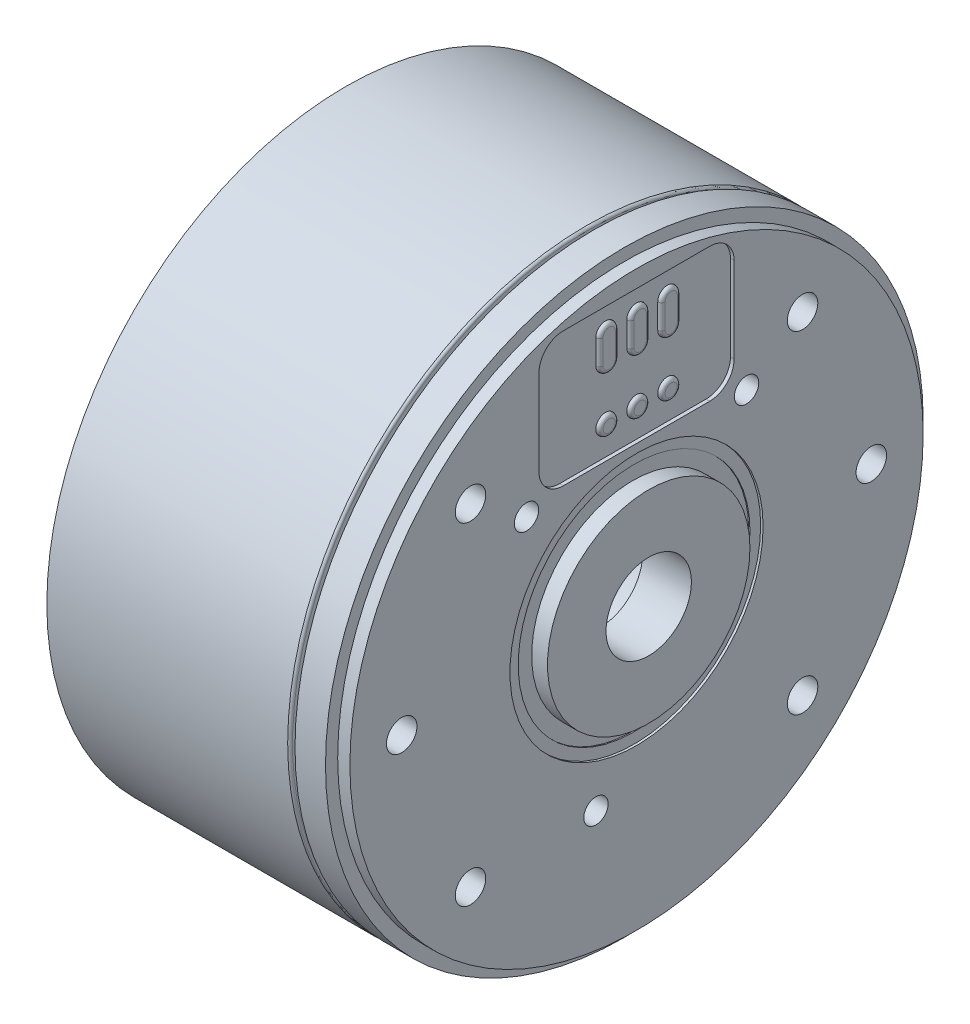
SolidWorks part; units mm, degrees
material "可锻铸铁"
ref_plane "前视基准面" through (0, 0, 0) normal (0, 0, 1) x (1, 0, 0)
ref_plane "上视基准面" through (0, 0, 0) normal (0, 1, 0) x (1, 0, 0)
ref_plane "右视基准面" through (0, 0, 0) normal (1, 0, 0) x (0, 0, -1)
sketch "草图2" plane through (0, 0, 0) normal (1, 0, 0) x (0, 0, -1)
  line L0 (0, 27.8437) -> (0, -27.533) construction
  line L1 (29.402, 0) -> (-30.6739, 0) construction
  line L2 (0, 0) -> (17.9277, 17.9277) construction
  circle A0 centre (0, 0) radius 24.5
  circle A1 centre (0, 0) radius 23.5
  circle A2 centre (0, 0) radius 12.5 construction
  circle A3 centre (0, 0) radius 9.5 construction
  circle A4 centre (0, 0) radius 6.3
  circle A5 centre (0, 9.5) radius 1.5
  circle A6 centre (9.5, 0) radius 1.5
  circle A7 centre (0, -9.5) radius 1.5
  circle A8 centre (-9.5, 0) radius 1.5
  circle A13 centre (8.8388, 8.8388) radius 1.5
  circle A14 centre (0, 0) radius 23.5
  circle A15 centre (8.8388, -8.8388) radius 1.5
  circle A16 centre (0, 0) radius 23.5
  circle A17 centre (-8.8388, -8.8388) radius 1.5
  circle A18 centre (0, 0) radius 23.5
  circle A19 centre (-8.8388, 8.8388) radius 1.5
  circle A20 centre (0, 0) radius 3.5
  point P17 (0, 0)
  point P27 (0, 0)
  point P36 (0, 0)
  dimension "D1" = 4
  dimension "D2" = 4
  dimension "D3" = 12.6
  dimension "D4" = 19
  dimension "D5" = 25
  dimension "D6" = 47
  dimension "D7" = 49
  dimension "D8" = 3
  dimension "D10" = 3
  dimension "D11" = 7
  dimension "D9" = 45
extrude "凸台-拉伸1" add sketch "草图2" along normal blind 24 contours A0
extrude "切除-拉伸18" cut sketch "草图2<17>" along normal blind 21.5 contours A0
sketch "草图2<17>" plane through (0, 0, 0) normal (1, 0, 0) x (0, 0, -1) same geometry as "草图2"
extrude "凸台-拉伸7" add sketch "草图2<18>" along normal blind 21.1 separate body contours A0
sketch "草图2<18>" plane through (0, 0, 0) normal (1, 0, 0) x (0, 0, -1) same geometry as "草图2"
extrude "凸台-拉伸2" add sketch "草图2<5>" along normal blind 25 contours A1
sketch "草图2<5>" plane through (0, 0, 0) normal (1, 0, 0) x (0, 0, -1) same geometry as "草图2"
extrude "切除-拉伸12" cut sketch "草图2<14>" along normal blind 4 contours A5 | A19 | A8 | A17 | A7 | A15 | A6 | A13 region at (0, 9.5, 0) region at (0, 0, -9.5) region at (0, -9.5, 0) region at (0, 0, 9.5) region at (0, 8.8388, -8.8388) region at (0, -8.8388, -8.8388) region at (0, -8.8388, 8.8388) region at (0, 8.8388, 8.8388)
sketch "草图2<14>" plane through (0, 0, 0) normal (1, 0, 0) x (0, 0, -1) same geometry as "草图2"
chamfer "倒角1" distance 2 angle 30 1 edges at (0, 0, -24.5) first distance on face at (0, 8.8388, -10.3388)
extrude "切除-拉伸13" cut sketch "草图2<15>" along normal blind 22 contours A4 region at (0, 0, 6.1218)
sketch "草图2<15>" plane through (0, 0, 0) normal (1, 0, 0) x (0, 0, -1) same geometry as "草图2"
extrude "切除-拉伸16" cut sketch "草图2<16>" along normal blind 27 contours A20
sketch "草图2<16>" plane through (0, 0, 0) normal (1, 0, 0) x (0, 0, -1) same geometry as "草图2"
ref_plane "基准面1" through (25, 0, 0) normal (1, 0, 0) x (0, 0, -1)
sketch "草图3" plane through (25, 0, 0) normal (1, 0, 0) x (0, 0, -1)
  line L0 (0, 0) -> (-16.0734, 18.4904) construction
  line L1 (0, 0) -> (16.0734, 18.4904) construction
  line L2 (0, 0) -> (-5.9271, -23.7722) construction
  line L3 (0, 38.8973) -> (0, -36.0973) construction
  line L4 (-43.5544, 0) -> (45.654, 0) construction
  line L5 (0, 0) -> (21.7406, 21.7406) construction
  line L6 (0, 10.3773) -> (0, 11.0773) construction
  line L7 (-6, 11.0773) -> (6, 11.0773)
  line L8 (8, 13.0773) -> (8, 20.0773)
  line L9 (-6, 22.0773) -> (6, 22.0773)
  line L10 (-8, 13.0773) -> (-8, 20.0773)
  line L11 (0, 20.25) -> (0, 18.25) construction
  line L12 (0.8, 20.25) -> (0.8, 18.25)
  line L13 (-0.8, 20.25) -> (-0.8, 18.25)
  line L14 (1.74, 20.25) -> (1.74, 18.25)
  line L15 (3.34, 20.25) -> (3.34, 18.25)
  line L16 (2.54, 20.25) -> (2.54, 18.25) construction
  line L17 (-2.54, 20.25) -> (-2.54, 18.25) construction
  line L18 (-1.74, 20.25) -> (-1.74, 18.25)
  line L19 (-3.34, 20.25) -> (-3.34, 18.25)
  circle A0 centre (0, 0) radius 13.75 construction
  circle A1 centre (0, 0) radius 19.25 construction
  circle A16 centre (0, 0) radius 24.5 construction
  circle A17 centre (0, 0) radius 8.3
  circle A19 centre (9.0208, 10.3773) radius 1
  circle A20 centre (-9.0208, 10.3773) radius 1
  circle A21 centre (-3.3264, -13.3416) radius 1
  circle A23 centre (13.6118, 13.6118) radius 1.25
  circle A24 centre (13.6118, -13.6118) radius 1.25
  circle A25 centre (-13.6118, -13.6118) radius 1.25
  circle A26 centre (-13.6118, 13.6118) radius 1.25
  circle A28 centre (0, 0) radius 3.5
  circle A29 centre (0, 0) radius 10.3773
  circle A30 centre (0, 0) radius 9.5
  arc A31 (-6, 11.0773) -> (-8, 13.0773) centre (-6, 13.0773) cw
  arc A32 (6, 11.0773) -> (8, 13.0773) centre (6, 13.0773) ccw
  arc A33 (8, 20.0773) -> (6, 22.0773) centre (6, 20.0773) ccw
  arc A34 (-6, 22.0773) -> (-8, 20.0773) centre (-6, 20.0773) ccw
  arc A35 (0.8, 20.25) -> (-0.8, 20.25) centre (0, 20.25) ccw
  arc A36 (-0.8, 18.25) -> (0.8, 18.25) centre (0, 18.25) ccw
  arc A37 (3.34, 20.25) -> (1.74, 20.25) centre (2.54, 20.25) ccw
  arc A38 (1.74, 18.25) -> (3.34, 18.25) centre (2.54, 18.25) ccw
  arc A39 (-1.74, 20.25) -> (-3.34, 20.25) centre (-2.54, 20.25) ccw
  arc A40 (-3.34, 18.25) -> (-1.74, 18.25) centre (-2.54, 18.25) ccw
  circle A41 centre (0, 13.75) radius 0.8
  circle A42 centre (2.54, 13.75) radius 0.8
  circle A43 centre (-2.54, 13.75) radius 0.8
  circle A44 centre (19.25, 0) radius 1.25
  circle A45 centre (-19.25, 0) radius 1.25
  point P15 (0, 0)
  point P16 (0, 0)
  point P33 (0, 0)
  point P45 (0, 22.0773)
  point P47 (-8, 11.0773)
  point P50 (8, 11.0773)
  point P56 (0, 19.25)
  point P64 (2.54, 19.25)
  point P71 (-2.54, 19.25)
  dimension "D2" = 16.6
  dimension "D3" = 2
  dimension "D5" = 27.5
  dimension "D7" = 38.5
  dimension "D8" = 82
  dimension "D9" = 2
  dimension "D10" = 2
  dimension "D11" = 4
  dimension "D12" = 45
  dimension "D13" = 2.5
  dimension "D14" = 7
  dimension "D15" = 20.7545
  dimension "D19" = 2
  dimension "D18" = 0.8
  dimension "D26" = 1.6
  dimension "D31" = 2.5
  dimension "D4" = 14
  dimension "D6" = 49
  dimension "D16" = 0.7
  dimension "D17" = 8
  dimension "D20" = 1.8273
  dimension "D21" = 2
  dimension "D24" = 2.54
  dimension "D25" = 2.54
  dimension "D29" = 5.08
  dimension "D30" = 2.54
  dimension "D22" = 2
  dimension "D23" = 2
  dimension "D27" = 2
  dimension "D28" = 2
extrude "凸台-拉伸6" add sketch "草图3" along normal blind 1 contours A17 region at (25, 0, 8.0652)
extrude "切除-拉伸17" cut sketch "草图3<7>" against normal blind 4 contours A23 | A24 | A21 | A25 | A26 | A45 | A44 | A19 | A20 region at (25, -13.3416, 3.3264) region at (25, 13.6118, -13.6118) region at (25, -13.6118, -13.6118) region at (25, -13.6118, 13.6118) region at (25, 13.6118, 13.6118) region at (25, 0, -19.25) region at (25, 0, 19.25)
sketch "草图3<7>" plane through (25, 0, 0) normal (1, 0, 0) x (0, 0, -1) same geometry as "草图3"
extrude "切除-拉伸19" cut sketch "草图3<8>" against normal blind 0.3 contours A30 A17 region at (25, 0, 9.2313)
sketch "草图3<8>" plane through (25, 0, 0) normal (1, 0, 0) x (0, 0, -1) same geometry as "草图3"
extrude "切除-拉伸20" cut sketch "草图3<9>" against normal blind 0.2 contours A29 A30 region at (25, 0, 10.0837)
sketch "草图3<9>" plane through (25, 0, 0) normal (1, 0, 0) x (0, 0, -1) same geometry as "草图3"
extrude "切除-拉伸21" cut sketch "草图3<10>" against normal blind 0.3 contours L8 A33 L9 A34 L10 A31 L7 A32
sketch "草图3<10>" plane through (25, 0, 0) normal (1, 0, 0) x (0, 0, -1) same geometry as "草图3"
extrude "凸台-拉伸8" add sketch "草图3<12>" along normal blind 0.3 separate body contours L19 A40 L18 A39 | L14 A38 L15 A37 | L12 A36 L13 A35 region at (25, 19.25, -2.54) region at (25, 19.25, 2.54)
sketch "草图3<12>" plane through (25, 0, 0) normal (1, 0, 0) x (0, 0, -1) same geometry as "草图3"
fillet "圆角1" radius 0.3 4 edges at (25.3, 21.05, 2.54) (25.3, 19.25, 3.34) (25.3, 17.45, 2.54) (25.3, 19.25, 1.74)
fillet "圆角2" radius 0.3 4 edges at (25.3, 21.05, 0) (25.3, 19.25, 0.8) (25.3, 17.45, 0) (25.3, 19.25, -0.8)
fillet "圆角3" radius 0.3 4 edges at (25.3, 21.05, -2.54) (25.3, 19.25, -1.74) (25.3, 17.45, -2.54) (25.3, 19.25, -3.34)
extrude "凸台-拉伸9" add sketch "草图3<13>" along normal blind 0.3 separate body contours A42 | A43 | A41 region at (25, 13.75, -2.54) region at (25, 13.75, 2.54)
sketch "草图3<13>" plane through (25, 0, 0) normal (1, 0, 0) x (0, 0, -1) same geometry as "草图3"
fillet "圆角4" radius 0.3 1 edges at (25.3, 13.75, 1.74)
fillet "圆角5" radius 0.3 1 edges at (25.3, 13.75, -0.8)
fillet "圆角6" radius 0.3 1 edges at (25.3, 13.75, -3.34)
fillet "圆角7" radius 0.2 1 edges at (21.1, 0, -24.5)
